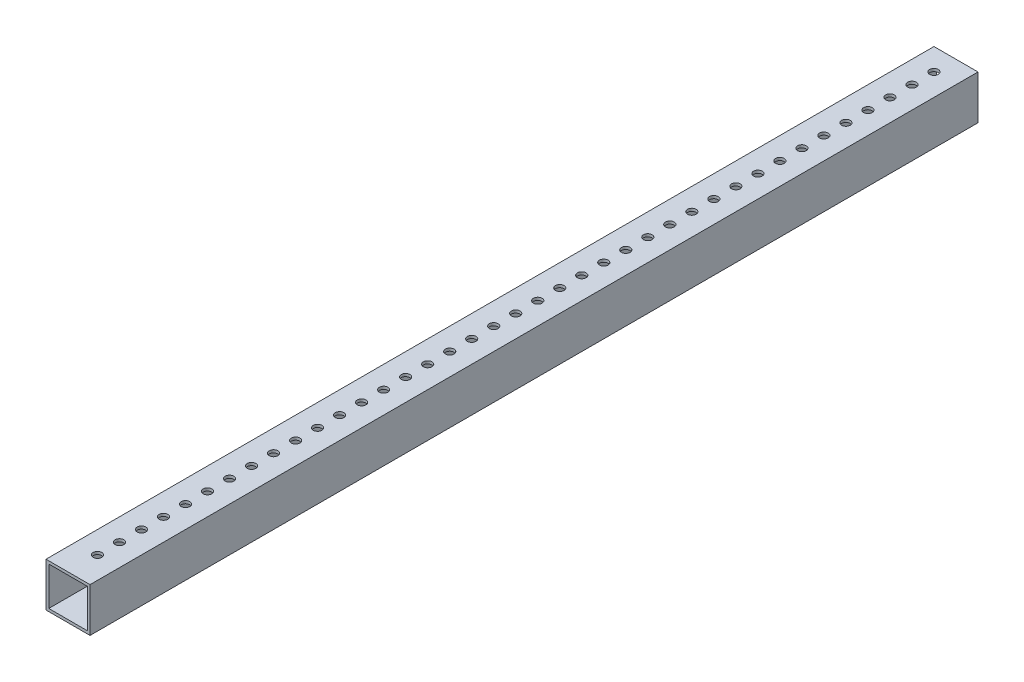
SolidWorks part; units mm, degrees
material "6061-T6 (SS)"
ref_plane "Front Plane" through (0, 0, 0) normal (0, 0, 1) x (1, 0, 0)
ref_plane "Top Plane" through (0, 0, 0) normal (0, 1, 0) x (1, 0, 0)
ref_plane "Right Plane" through (0, 0, 0) normal (1, 0, 0) x (0, 0, -1)
sketch "Sketch1" plane through (0, 0, 0) normal (0, 0, 1) x (1, 0, 0)
  line L1 (-12.7, -12.7) -> (12.7, -12.7)
  line L2 (-12.7, -12.7) -> (-12.7, 12.7)
  line L3 (-12.7, 12.7) -> (12.7, 12.7)
  line L4 (12.7, -12.7) -> (12.7, 12.7)
  line L5 (-12.7, -12.7) -> (12.7, 12.7) construction
  line L6 (-12.7, 12.7) -> (12.7, -12.7) construction
  point P0 (0, 0)
  dimension "D1" = 25.4
  dimension "D2" = 25.4
extrude "Boss-Extrude1" add sketch "Sketch1" along normal mid plane 512.2914
shell "Shell1" thickness 1.5875 removed face at (0, 0, -256.1457) removed face at (0, 0, 256.1457)
sketch "Sketch3" plane through (0, 0, 0) normal (0, 1, 0) x (1, 0, 0)
  line L0 (12.7, 256.1457) -> (-12.7, 256.1457) construction
  circle A0 centre (0, 243.4457) radius 2.4892
  circle A1 centre (0, 230.7457) radius 2.4892
  circle A2 centre (0, 218.0457) radius 2.4892
  circle A3 centre (0, 205.3457) radius 2.4892
  circle A4 centre (0, 192.6457) radius 2.4892
  circle A5 centre (0, 179.9457) radius 2.4892
  circle A6 centre (0, 167.2457) radius 2.4892
  circle A7 centre (0, 154.5457) radius 2.4892
  circle A8 centre (0, 141.8457) radius 2.4892
  circle A9 centre (0, 129.1457) radius 2.4892
  circle A10 centre (0, 116.4457) radius 2.4892
  circle A11 centre (0, 103.7457) radius 2.4892
  circle A12 centre (0, 91.0457) radius 2.4892
  circle A13 centre (0, 78.3457) radius 2.4892
  circle A14 centre (0, 65.6457) radius 2.4892
  circle A15 centre (0, 52.9457) radius 2.4892
  circle A16 centre (0, 40.2457) radius 2.4892
  circle A17 centre (0, 27.5457) radius 2.4892
  circle A18 centre (0, 14.8457) radius 2.4892
  circle A19 centre (0, 2.1457) radius 2.4892
  circle A20 centre (0, -10.5543) radius 2.4892
  circle A21 centre (0, -23.2543) radius 2.4892
  circle A22 centre (0, -35.9543) radius 2.4892
  circle A23 centre (0, -48.6543) radius 2.4892
  circle A24 centre (0, -61.3543) radius 2.4892
  circle A25 centre (0, -74.0543) radius 2.4892
  circle A26 centre (0, -86.7543) radius 2.4892
  circle A27 centre (0, -99.4543) radius 2.4892
  circle A28 centre (0, -112.1543) radius 2.4892
  circle A29 centre (0, -124.8543) radius 2.4892
  circle A30 centre (0, -137.5543) radius 2.4892
  circle A31 centre (0, -150.2543) radius 2.4892
  circle A32 centre (0, -162.9543) radius 2.4892
  circle A33 centre (0, -175.6543) radius 2.4892
  circle A34 centre (0, -188.3543) radius 2.4892
  circle A35 centre (0, -201.0543) radius 2.4892
  circle A36 centre (0, -213.7543) radius 2.4892
  circle A37 centre (0, -226.4543) radius 2.4892
  circle A38 centre (0, -239.1543) radius 2.4892
  point P4 (0, 256.1457)
  dimension "D1" = 4.9784
  dimension "D2" = 12.7
  dimension "D4" = 12.7
  dimension "D3" = 39
extrude "Cut-Extrude1" cut sketch "Sketch3" against normal through all both and the other way through all
